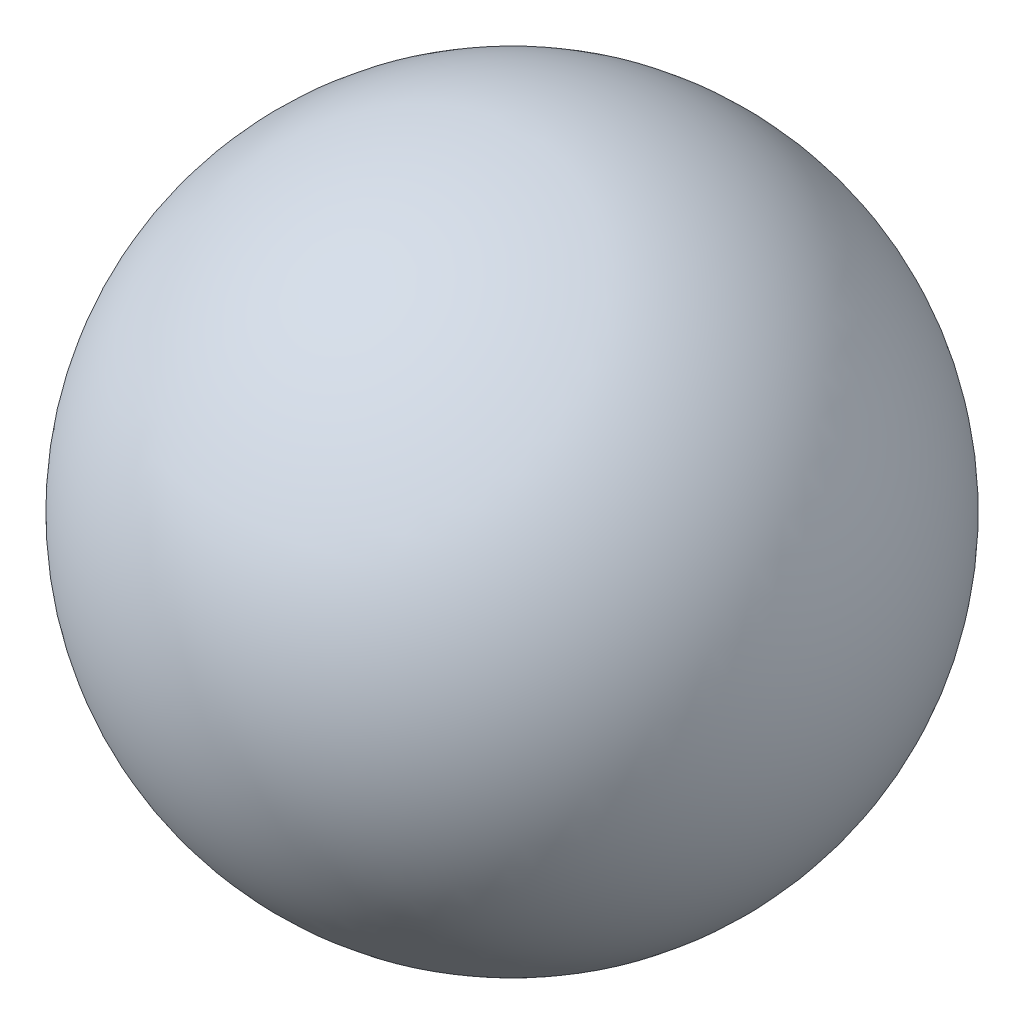
SolidWorks part; units mm, degrees
ref_plane "Front Plane" through (0, 0, 0) normal (0, 0, 1) x (1, 0, 0)
ref_plane "Top Plane" through (0, 0, 0) normal (0, 1, 0) x (1, 0, 0)
ref_plane "Right Plane" through (0, 0, 0) normal (1, 0, 0) x (0, 0, -1)
sketch "Sketch1" plane through (0, 0, 0) normal (0, 0, 1) x (1, 0, 0)
  line L0 (0, 11) -> (0, -11)
  arc A0 (0, 11) -> (0, -11) centre (0, 0) ccw
  point P4 (0, 0)
  dimension "D1" = 11
ref_axis "Axis1" through (0, 24.2, 0) along (0, -1, 0)
revolve "Revolve1" add sketch "Sketch1" angle 360 about L0
